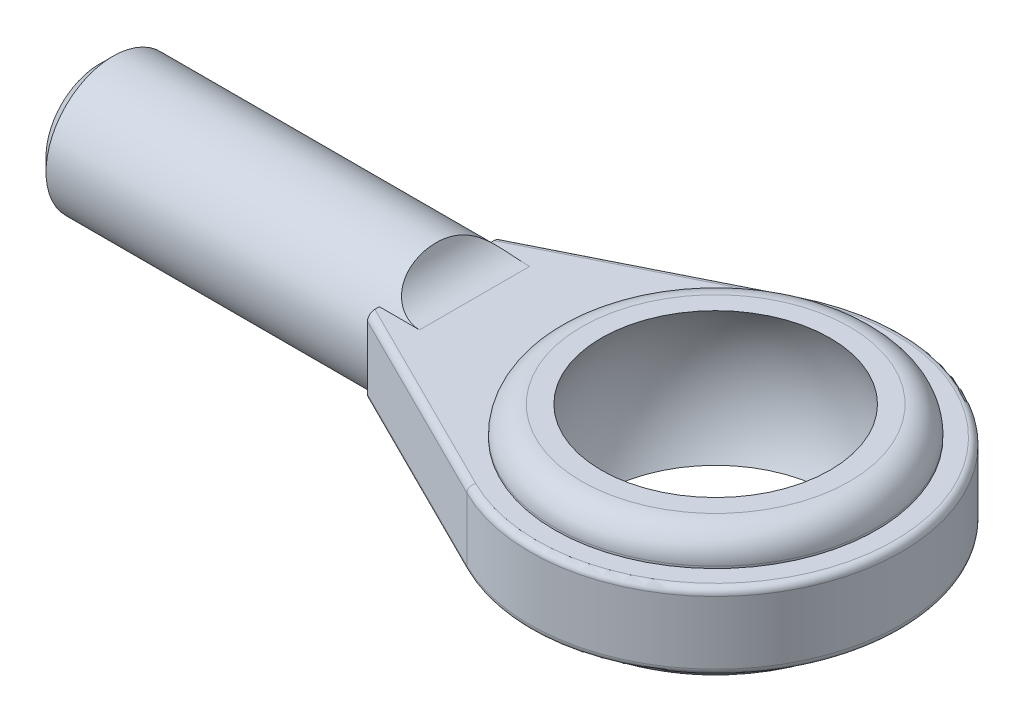
SolidWorks part; units mm, degrees
material "AISI 304"
ref_plane "Front Plane" through (0, 0, 0) normal (0, 0, 1) x (1, 0, 0)
ref_plane "Top Plane" through (0, 0, 0) normal (0, 1, 0) x (1, 0, 0)
ref_plane "Right Plane" through (0, 0, 0) normal (1, 0, 0) x (0, 0, -1)
sketch "Sketch1" plane through (0, 0, 0) normal (1, 0, 0) x (0, 0, -1)
  circle A0 centre (0, 0) radius 5
  dimension "D1" = 10
extrude "Boss-Extrude1" add sketch "Sketch1" along normal blind 25
chamfer "Chamfer1" distance 1 angle 45 1 edges at (0, 0, -5)
sketch "Sketch2" plane through (0, 0, 0) normal (0, 1, 0) x (1, 0, 0)
  line L0 (39.8163, 12.3929) -> (25, 5)
  line L1 (25, 5) -> (25, -5)
  line L2 (25, -5) -> (39.8163, -12.3929)
  circle A0 centre (46, 0) radius 13.85
  dimension "D1" = 27.7
  dimension "D2" = 21
extrude "Boss-Extrude2" add sketch "Sketch2" along normal mid plane 5.7 contours A0 L0 L1 L2 | A0 region at (29.8815, 0, 0) region at (46, 0, 0)
fillet "Fillet1" radius 0.5 6 edges at (32.4081, -2.85, 8.6965) (59.85, -2.85, 0) (32.4081, 2.85, -8.6965) (59.85, 2.85, 0) (32.4081, -2.85, -8.6965) (32.4081, 2.85, 8.6965)
fillet "Fillet2" radius 3 2 edges at (25, -2.85, 0) (25, 2.85, 0)
sketch "Sketch5" plane through (0, 0, 0) normal (0, 1, 0) x (1, 0, 0)
  circle A0 centre (46, 0) radius 12
  dimension "D1" = 24
extrude "Boss-Extrude3" add sketch "Sketch5" along normal mid plane 10
fillet "Fillet3" radius 2 2 edges at (46, -5, 12) (46, 5, 12)
sketch "Sketch4" plane through (0, 0, 0) normal (0, 1, 0) x (1, 0, 0)
  line L0 (46, 9.9) -> (46, -9.9)
  arc A0 (46, -9.9) -> (46, 9.9) centre (46, 0) ccw
  dimension "D1" = 19.8
revolve "Cut-Revolve1" cut sketch "Sketch4" angle 360 about L0
